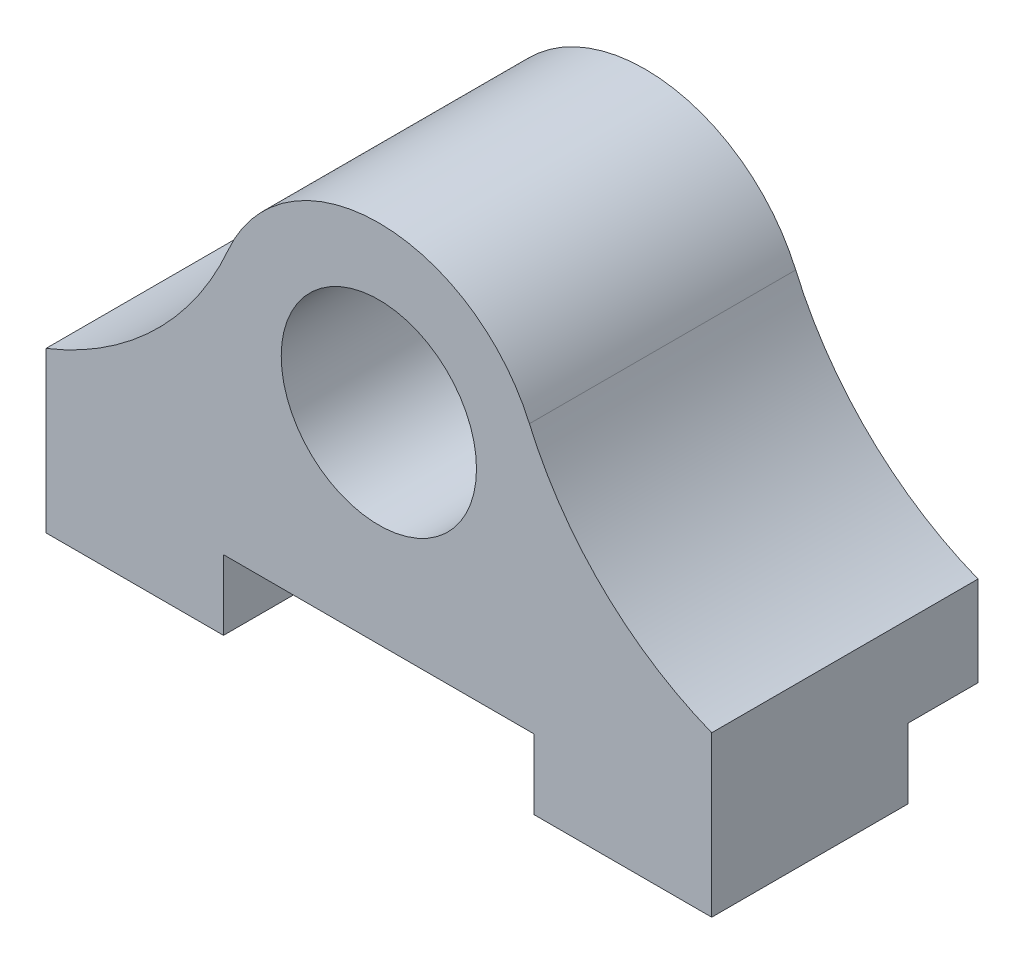
SolidWorks part; units mm, degrees
ref_plane "Front Plane" through (0, 0, 0) normal (0, 0, 1) x (1, 0, 0)
ref_plane "Top Plane" through (0, 0, 0) normal (0, 1, 0) x (1, 0, 0)
ref_plane "Right Plane" through (0, 0, 0) normal (1, 0, 0) x (0, 0, -1)
sketch "Sketch1" plane through (0, 0, 0) normal (0, 0, 1) x (1, 0, 0)
  line L0 (-15, -5) -> (15, -5)
  circle A0 centre (0, 0) radius 4.4
  arc A1 (-6.7851, 2.9534) -> (6.7851, 2.9534) centre (0, 0) cw
  arc A2 (6.7851, 2.9534) -> (15, -5) centre (20.5387, 8.94) ccw
  arc A3 (-6.7851, 2.9534) -> (-15, -5) centre (-20.5387, 8.94) cw
  point P12 (0, -5)
  dimension "D1" = 8.8
  dimension "D2" = 3
  dimension "D3" = 5
  dimension "D5" = 15
  dimension "D4" = 30
extrude "Boss-Extrude1" add sketch "Sketch1" along normal blind 10
extrude "Boss-Extrude2" add sketch "Sketch1<2>" against normal blind 2 contours A0 | A1 A3 L0 A2 A0 region at (-9.8792, -2.07, 0) region at (0, 0, 0)
sketch "Sketch1<2>" plane through (0, 0, 0) normal (0, 0, 1) x (1, 0, 0) same geometry as "Sketch1"
sketch "Sketch3" plane through (0, -5, 0) normal (0, -1, 0) x (1, 0, 0)
  line L1 (-15, 10) -> (15, 10)
  line L2 (-15, 10) -> (-15, -2)
  line L3 (-15, -2) -> (15, -2)
  line L4 (15, 10) -> (15, -2)
extrude "Boss-Extrude4" add sketch "Sketch3" along normal blind 7.2
sketch "Sketch2" plane through (0, 0, 0) normal (0, 1, 0) x (1, 0, 0)
  line L1 (-8, -8) -> (-15, -8)
  line L2 (-8, -8) -> (-8, 0)
  line L3 (-8, 0) -> (-15, 0)
  line L4 (-15, -8) -> (-15, 0)
  line L5 (-8, -8) -> (-15, 0) construction
  line L6 (-8, 0) -> (-15, -8) construction
  line L8 (8, -8) -> (15, -8)
  line L9 (8, -8) -> (8, 0)
  line L10 (8, 0) -> (15, 0)
  line L11 (15, -8) -> (15, 0)
  line L12 (8, -8) -> (15, 0) construction
  line L13 (8, 0) -> (15, -8) construction
  line L15 (-15, -10) -> (-15, 2) construction
  line L16 (15, -10) -> (15, 2) construction
  circle A0 centre (11.5, -4) radius 1.65
  circle A1 centre (-11.5, -4) radius 1.65
  point P0 (-11.5, -4)
  point P7 (11.5, -4)
  point P12 (15, -4)
  dimension "D3" = 3.3
  dimension "D1" = 8
  dimension "D2" = 7
extrude "Cut-Extrude2" cut sketch "Sketch2" along normal blind 8 from surface contours A1 | A0 region at (-11.5, 0, 4) starting at face at (0, -12.2, 4)
sketch "Sketch5" plane through (0, 0, -2) normal (0, 0, -1) x (-1, 0, 0)
  line L0 (-15, -12.2) -> (-15, -5) construction
  line L1 (-15, -12.2) -> (15, -12.2)
  line L2 (-15, -12.2) -> (-15, -9.05)
  line L3 (-15, -9.05) -> (15, -9.05)
  line L4 (15, -12.2) -> (15, -9.05)
  line L5 (15, -12.2) -> (15, -5) construction
  line L6 (15, -12.2) -> (-15, -12.2) construction
  dimension "D1" = 3.15
extrude "Cut-Extrude3" cut sketch "Sketch5" against normal blind 3.15 and the other way through all
sketch "Sketch6" plane through (0, 0, 10) normal (0, 0, 1) x (1, 0, 0)
  line L0 (15, -12.2) -> (-15, -12.2) construction
  line L1 (-7, -12.2) -> (7, -12.2)
  line L2 (-7, -12.2) -> (-7, -9.05)
  line L3 (-7, -9.05) -> (7, -9.05)
  line L4 (7, -12.2) -> (7, -9.05)
  line L5 (-7, -12.2) -> (7, -9.05) construction
  line L6 (-7, -9.05) -> (7, -12.2) construction
  point P0 (0, -10.625)
  dimension "D1" = 3.15
  dimension "D2" = 14
extrude "Cut-Extrude4" cut sketch "Sketch6" against normal through all both and the other way through all
